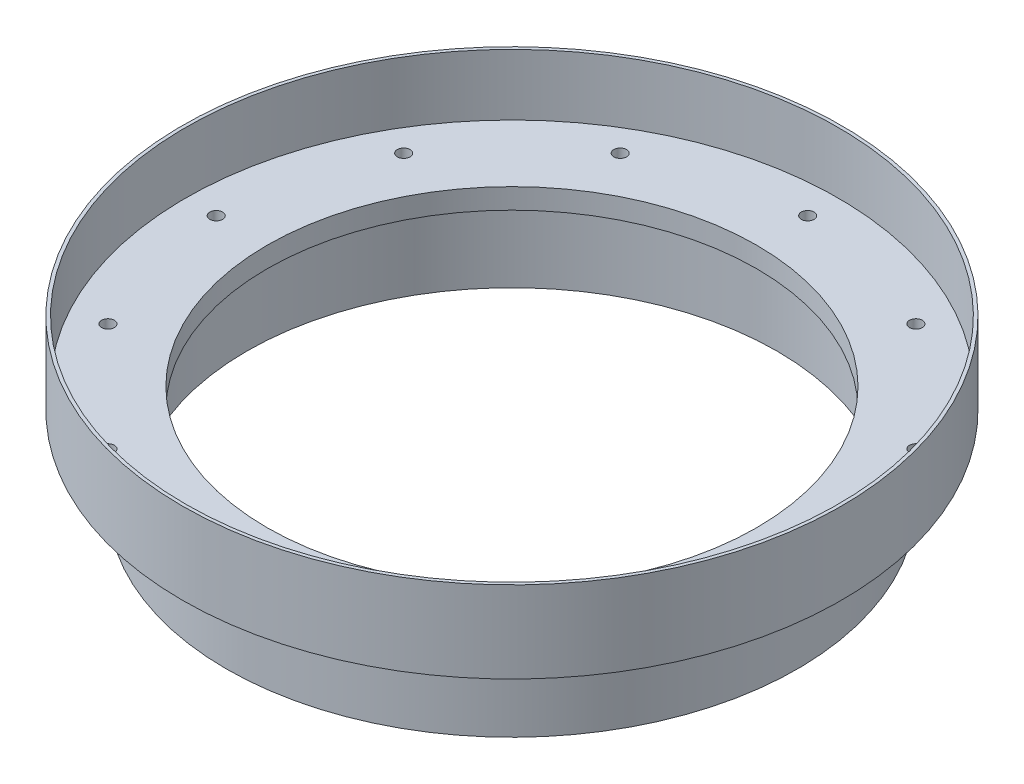
SolidWorks part; units mm, degrees
material "6061-T6 (SS)"
ref_plane "Front Plane" through (0, 0, 0) normal (0, 0, 1) x (1, 0, 0)
ref_plane "Top Plane" through (0, 0, 0) normal (0, 1, 0) x (1, 0, 0)
ref_plane "Right Plane" through (0, 0, 0) normal (1, 0, 0) x (0, 0, -1)
ref_axis "Axis1" through (0, 55, 0) along (0, -1, 0)
sketch "Cross Section" plane through (0, 0, 0) normal (0, 0, 1) x (1, 0, 0)
  line L0 (-38.1, 0) -> (-38.1, -3.175)
  line L1 (-38.1, -3.175) -> (-41.275, -3.175)
  line L2 (-41.275, -3.175) -> (-41.275, -15.875)
  line L4 (0, -15.875) -> (-38.1, -15.875) construction
  line L5 (-44.45, -15.875) -> (-44.45, -3.175)
  line L6 (-44.45, -3.175) -> (-51.308, -3.175)
  line L7 (-51.308, -3.175) -> (-51.308, 9.525)
  line L8 (-51.308, 9.525) -> (-50.8, 9.525)
  line L9 (-50.8, 9.525) -> (-50.8, 0)
  line L10 (-50.8, 0) -> (-38.1, 0)
  line L11 (-38.1, 0) -> (0, 0) construction
  line L12 (0, 55) -> (0, -55) construction
  line L13 (-44.45, -15.875) -> (-41.275, -15.875)
  line L14 (-50.8, 1.5875) -> (-50.8, 3.175) construction
  dimension "D1" = 3.175
  dimension "D3" = 3.175
  dimension "D5" = 6.858
  dimension "D6" = 12.7
  dimension "D9" = 3.175
  dimension "D8" = 38.1
revolve "Main" add sketch "Cross Section" angle 360 about axis through (0, 55, 0) along (0, -1, 0)
sketch "Hole Location" plane through (0, 0, 0) normal (0, 1, 0) x (1, 0, 0)
  line L0 (0, 0) -> (-46.0375, 0) construction
  circle A0 centre (0, 0) radius 46.0375 construction
  dimension "D1" = 92.075
hole_wizard "#3-48 Tapped Hole1" positions "Sketch5" profile "Sketch7" tap size "#3-48" standard "ANSI Inch"
sketch "Sketch5" plane through (0, 0, 0) normal (0, 1, 0) x (1, 0, 0)
  point P0 (-46.0375, 0)
sketch "Sketch7" plane through (-46.0375, 0, 0) normal (1, 0, 0) x (0, 0, 1)
  line L0 (0, 0) -> (0, 3.901)
  line L1 (0, 3.901) -> (0.9969, 3.302)
  line L2 (0.9969, 3.302) -> (0.9969, 0)
  line L5 (0.9969, 0) -> (0, 0)
  line L10 (0, 3.901) -> (-0.997, 3.302) construction
  line L11 (0, -6.35) -> (0, 107.95) construction
  dimension "Tap Drill Dia." = 1.9939
  dimension "Tap Drill Depth" = 3.302
  dimension "Drill Angle" = 118
cosmetic thread "Hole Thread1" parameters "D1"=3.175, "D2"=2.5146
pattern_circular "Screw Holes" count 12 over 360 about axis through (0, 55, 0) along (0, -1, 0) of "#3-48 Tapped Hole1"
equation "\"D8@Cross Section\"=\"TANK DIAMETER@Cryo Tank.Assembly\"/2"
equation "\"D1@Hole Location\"=\"TANK DIAMETER@Cryo Tank.Assembly\"+\"GASKET SEAT THICKNESS@Cryo Tank.Assembly\"+\"LINER THICKNESS@Cryo Tank.Assembly\""
equation "\"D1@Cross Section\"=\"LINER THICKNESS@Cryo Tank.Assembly\""
equation "\"D3@Cross Section\"=\"ALUMINUM LAP THICKNESS@Cryo Tank.Assembly\""
equation "\"D5@Cross Section\"=2*\"CF THICKNESS@Cryo Tank.Assembly\"+\"NOMEX THICKNESS@Cryo Tank.Assembly\""
